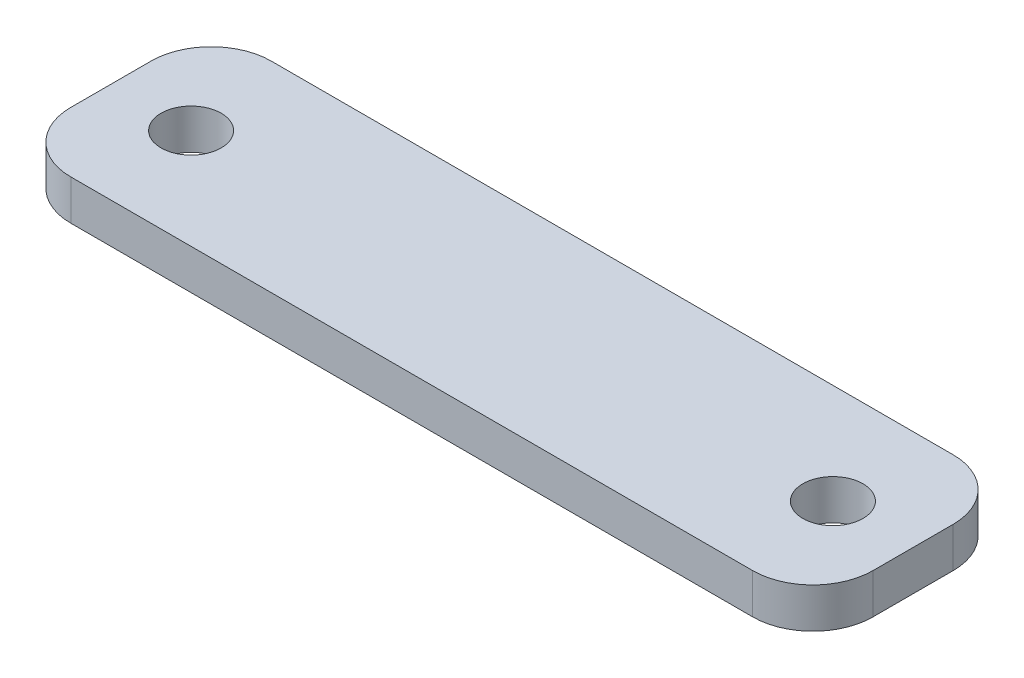
SolidWorks part; units mm, degrees
ref_plane "Front Plane" through (0, 0, 0) normal (0, 0, 1) x (1, 0, 0)
ref_plane "Top Plane" through (0, 0, 0) normal (0, 1, 0) x (1, 0, 0)
ref_plane "Right Plane" through (0, 0, 0) normal (1, 0, 0) x (0, 0, -1)
sketch "Sketch1" plane through (0, 0, 0) normal (0, 1, 0) x (1, 0, 0)
  line L1 (-20, 5) -> (20, 5)
  line L2 (-20, 5) -> (-20, -5)
  line L3 (-20, -5) -> (20, -5)
  line L4 (20, 5) -> (20, -5)
  line L5 (-20, 5) -> (20, -5) construction
  line L6 (-20, -5) -> (20, 5) construction
  point P0 (0, 0)
  dimension "D1" = 10
  dimension "D2" = 40
extrude "Boss-Extrude1" add sketch "Sketch1" along normal blind 2
sketch "Sketch2" plane through (0, 2, 0) normal (0, 1, 0) x (1, 0, 0)
  point P10 (26.3156, 0)
fillet "Fillet1" radius 3 4 edges at (20, 1, 5) (20, 1, -5) (-20, 1, 5) (-20, 1, -5)
hole_wizard "Ø3.0mm Dowel Hole1" positions "Sketch5" profile "Sketch6" hole size "Ø3.0" standard "ISO" end condition through all
sketch "Sketch5" plane through (0, 0, 0) normal (0, -1, 0) x (-1, 0, 0)
  line L1 (-20, -2) -> (-20, 2) construction
  line L3 (20, 0) -> (-20, 0) construction
  line L4 (20, 2) -> (20, -2) construction
  line L5 (20, 2) -> (20, -2) construction
  point P0 (-16, 0)
  point P2 (16, 0)
  point P19 (15.2725, 0)
  dimension "D1" = 4
  dimension "D2" = 4
sketch "Sketch6" plane through (16, 0, 0) normal (1, 0, 0) x (0, 0, -1)
  line L0 (0, 0) -> (0, 2)
  line L1 (0, 2) -> (1.5, 2)
  line L2 (1.5, 2) -> (1.5, 0)
  line L5 (1.5, 0) -> (0, 0)
  line L11 (0, -6.35) -> (0, 107.95) construction
  dimension "Thru Hole Dia." = 3
  dimension "Thru Hole Depth" = 2
equation "\"globalength1\"=55"
